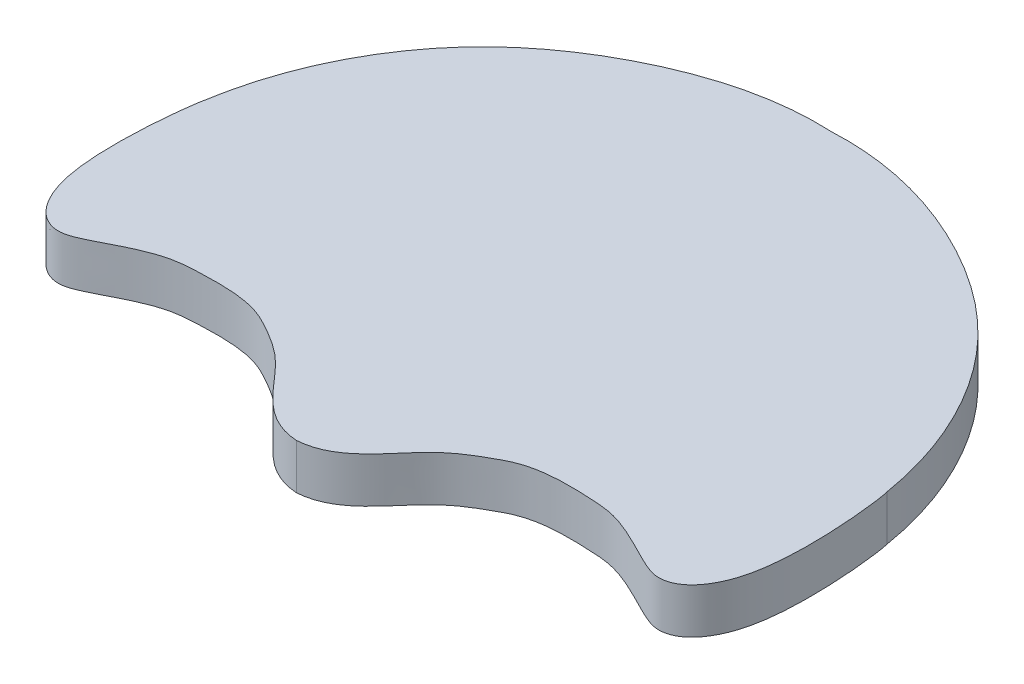
SolidWorks part; units mm, degrees
material "6061-T6 (SS)"
ref_plane "Front Plane" through (0, 0, 0) normal (0, 0, 1) x (1, 0, 0)
ref_plane "Top Plane" through (0, 0, 0) normal (0, 1, 0) x (1, 0, 0)
ref_plane "Right Plane" through (0, 0, 0) normal (1, 0, 0) x (0, 0, -1)
sketch "Sketch3" plane through (0, 0, 0) normal (0, 1, 0) x (1, 0, 0)
  line L0 (0, 0) -> (0, 159.1899) construction
  line L1 (0, 0) -> (0, -140.5301) construction
  line L2 (0, 0) -> (-190.5, 0) construction
  line L3 (0, 0) -> (190.5, 0) construction
  spline S0 degree 3 poles (-190.5, 0) (-184.3927, 37.537) (-157.2613, 93.9641) (-82.3875, 146.6227) (-31.3114, 160.7999) (0, 159.1899) knots 0 0 0 0 0.424401 0.65637 1 1 1 1
  spline S1 degree 3 poles (-190.5, 0) (-192.064, -4.9635) (-201.9672, -83.3146) (-174.6966, -109.29) (-151.6301, -100.568) (-131.4108, -87.7198) (-96.8436, -85.3754) (-78.6925, -86.2588) (-58.8335, -96.8794) (-37.3059, -109.9358) (-21.3496, -139.1148) (0, -140.5301) knots 0 0 0 0 0.166997 0.292321 0.319633 0.426735 0.458914 0.609242 0.64191 0.766802 1 1 1 1
  spline S2 degree 3 poles (190.5, 0) (192.064, -4.9635) (201.9672, -83.3146) (174.6966, -109.29) (151.6301, -100.568) (131.4108, -87.7198) (96.8436, -85.3754) (78.6925, -86.2588) (58.8335, -96.8794) (37.3059, -109.9358) (21.3496, -139.1148) (0, -140.5301) knots 0 0 0 0 0.166997 0.292321 0.319633 0.426735 0.458914 0.609242 0.64191 0.766802 1 1 1 1
  spline S3 degree 3 poles (190.5, 0) (184.3927, 37.537) (157.2613, 93.9641) (82.3875, 146.6227) (31.3114, 160.7999) (0, 159.1899) knots 0 0 0 0 0.424401 0.65637 1 1 1 1
  dimension "D1" = 381
  dimension "D2" = 299.72
  dimension "D3" = 159.1899
  dimension "D4" = 86.8953
  dimension "D5" = 104.4979
  dimension "D6" = 29.1616
  dimension "D7" = 92.2742
  dimension "D8" = 108.411
  dimension "D9" = 67.4883
  dimension "D10" = 43.7314
  dimension "D11" = 117.6915
  dimension "D12" = 162.2568
  dimension "D13" = 89.4522
  dimension "D14" = 140.1036
  dimension "D15" = 175.0666
  dimension "D16" = 50.2669
  dimension "D17" = 101.3666
  dimension "D18" = 138.1225
  dimension "D19" = 155.1557
  dimension "D20" = 192.0074
  dimension "D21" = 193.9268
  dimension "D23" = 76.6666
extrude "Boss-Extrude1" add sketch "Sketch3" along normal blind 25.4 from surface starting at plane "Top Plane"
sketch "Sketch5" plane through (0, 0, 0) normal (0, -1, 0) x (1, 0, 0)
  line L0 (0, 0) -> (0, -20.32) construction
  line L1 (31.75, -52.07) -> (-31.75, -52.07)
  line L2 (31.75, -52.07) -> (31.75, 11.43)
  line L3 (31.75, 11.43) -> (-31.75, 11.43)
  line L4 (-31.75, -52.07) -> (-31.75, 11.43)
  line L5 (31.75, -52.07) -> (-31.75, 11.43) construction
  line L6 (31.75, 11.43) -> (-31.75, -52.07) construction
  line L7 (-31.75, -52.07) -> (-31.75, -30.48)
  line L8 (-31.75, -30.48) -> (31.75, -30.48) construction
  line L9 (0, -20.32) -> (140.7253, -20.32) construction
  line L10 (0, -20.32) -> (0, -97.1287) construction
  line L11 (0, -20.32) -> (31.9753, -118.7297) construction
  line L13 (0, -20.32) -> (63.8443, -108.1942) construction
  line L14 (0, -20.32) -> (95.5392, -89.7333) construction
  line L15 (124.7166, -60.8429) -> (0, -20.32) construction
  line L16 (0, -20.32) -> (154.5508, 21.0918) construction
  line L17 (0, -20.32) -> (148.922, 65.6601) construction
  line L18 (0, -20.32) -> (-31.9753, -118.7297) construction
  line L19 (0, -20.32) -> (-63.8443, -108.1942) construction
  line L20 (0, -20.32) -> (-95.5392, -89.7333) construction
  line L21 (-124.7166, -60.8429) -> (0, -20.32) construction
  line L22 (0, -20.32) -> (-154.5508, 21.0918) construction
  line L23 (0, -20.32) -> (-148.922, 65.6601) construction
  spline S0 degree 3 poles (-148.922, 65.6601) (-157.8584, 40.2253) (-156.2837, 8.5854) (-143.1202, -28.9506) (-139.3242, -37.3463) (-130.3709, -53.1962) (-125.215, -60.649) (-118.0488, -69.1403) (-116.5795, -70.7975) (-113.5719, -74.0252) (-112.0368, -75.592) (-107.2801, -80.2116) (-103.9215, -83.1695) (-93.3361, -91.6595) (-85.5959, -96.8074) (-76.3408, -101.9556) (-75.3049, -102.5187) (-73.219, -103.6268) (-72.1677, -104.1726) (-69.0049, -105.7765) (-66.8862, -106.8006) (-60.5068, -109.7299) (-56.2231, -111.4921) (-47.6308, -114.6027) (-43.3223, -115.9511) (-34.7104, -118.209) (-30.4072, -119.1185) (-21.8242, -120.4791) (-17.5446, -120.9304) (-11.1443, -121.2499) (-9.0138, -121.2968) (-5.8216, -121.2757) (-4.1848, -121.2414) (-2.5489, -121.1705) (-1.9677, -121.1408) (-1.9605, -121.1404) (-1.2995, -121.1064) (-0.6497, -121.073) (0, -121.0396) knots -0.292878 -0.292878 -0.292878 -0.292878 0.125 0.125 0.25 0.25 0.375 0.375 0.40625 0.40625 0.4375 0.4375 0.5 0.5 0.625 0.625 0.640625 0.640625 0.65625 0.65625 0.6875 0.6875 0.75 0.75 0.8125 0.8125 0.875 0.875 0.9375 0.9375 0.96875 0.96875 0.984375 0.992798 0.992798 0.99292 0.99292 1 1 1 1
  spline S5 degree 3 poles (998.6789, -69.6893) (665.1581, -86.8384) (331.6156, -103.9885) (-1.9268, -121.1387) (-1.9605, -121.1404) (-1.9677, -121.1408) (-2.5489, -121.1705) (-4.1848, -121.2414) (-5.8216, -121.2757) (-9.0138, -121.2968) (-11.1443, -121.2499) (-17.5446, -120.9304) (-21.8242, -120.4791) (-30.4072, -119.1185) (-34.7104, -118.209) (-43.3223, -115.9511) (-47.6308, -114.6027) (-56.2231, -111.4921) (-60.5068, -109.7299) (-66.8862, -106.8006) (-69.0049, -105.7765) (-72.1677, -104.1726) (-73.219, -103.6268) (-75.3049, -102.5187) (-76.3408, -101.9556) (-85.5959, -96.8074) (-93.3361, -91.6595) (-103.9215, -83.1695) (-107.2801, -80.2116) (-112.0368, -75.592) (-113.5719, -74.0252) (-116.5795, -70.7975) (-118.0488, -69.1403) (-125.215, -60.649) (-130.3709, -53.1962) (-139.3242, -37.3463) (-143.1202, -28.9506) (-198.5095, 128.9933) (-22.362, 351.6373) (651.8169, -587.5188) knots -3.627409 -3.627409 -3.627409 -3.627409 0.006836 0.00708 0.00708 0.007202 0.007202 0.015625 0.03125 0.03125 0.0625 0.0625 0.125 0.125 0.1875 0.1875 0.25 0.25 0.3125 0.3125 0.34375 0.34375 0.359375 0.359375 0.375 0.375 0.5 0.5 0.5625 0.5625 0.59375 0.59375 0.625 0.625 0.75 0.75 0.875 0.875 3.034324 3.034324 3.034324 3.034324 only from (0, -121.0396) to (-152.8945, 6.1184)
  spline S6 degree 3 poles (-1687.8289, -2297.0686) (-150.4269, 537.0593) (218.9922, 187.4002) (143.1202, -28.9506) (139.3242, -37.3463) (130.3709, -53.1962) (125.215, -60.649) (118.0488, -69.1403) (116.5795, -70.7975) (113.5719, -74.0252) (112.0368, -75.592) (107.2801, -80.2116) (103.9215, -83.1695) (93.3361, -91.6595) (85.5959, -96.8074) (76.3408, -101.9556) (75.3049, -102.5187) (73.219, -103.6268) (72.1677, -104.1726) (69.0049, -105.7765) (66.8862, -106.8006) (60.5068, -109.7299) (56.2231, -111.4921) (47.6308, -114.6027) (43.3223, -115.9511) (34.7104, -118.209) (30.4072, -119.1185) (21.8242, -120.4791) (17.5446, -120.9304) (11.1443, -121.2499) (9.0138, -121.2968) (5.8216, -121.2757) (4.1848, -121.2414) (2.5489, -121.1705) (1.9677, -121.1408) (1.9605, -121.1404) (-997.3522, -69.7575) (-1996.6535, -18.3753) (-2996.029, 33.0152) knots -2.879056 -2.879056 -2.879056 -2.879056 0.125 0.125 0.25 0.25 0.375 0.375 0.40625 0.40625 0.4375 0.4375 0.5 0.5 0.625 0.625 0.640625 0.640625 0.65625 0.65625 0.6875 0.6875 0.75 0.75 0.8125 0.8125 0.875 0.875 0.9375 0.9375 0.96875 0.96875 0.984375 0.992798 0.992798 0.99292 0.99292 11.881939 11.881939 11.881939 11.881939 only from (152.8945, 6.1184) to (0, -121.0396)
  spline S8 degree 3 poles (148.922, 65.6601) (157.8584, 40.2253) (156.2837, 8.5854) (143.1202, -28.9506) (139.3242, -37.3463) (130.3709, -53.1962) (125.215, -60.649) (118.0488, -69.1403) (116.5795, -70.7975) (113.5719, -74.0252) (112.0368, -75.592) (107.2801, -80.2116) (103.9215, -83.1695) (93.3361, -91.6595) (85.5959, -96.8074) (76.3408, -101.9556) (75.3049, -102.5187) (73.219, -103.6268) (72.1677, -104.1726) (69.0049, -105.7765) (66.8862, -106.8006) (60.5068, -109.7299) (56.2231, -111.4921) (47.6308, -114.6027) (43.3223, -115.9511) (34.7104, -118.209) (30.4072, -119.1185) (21.8242, -120.4791) (17.5446, -120.9304) (11.1443, -121.2499) (9.0138, -121.2968) (5.8216, -121.2757) (4.1848, -121.2414) (2.5489, -121.1705) (1.9677, -121.1408) (1.9605, -121.1404) (1.2995, -121.1064) (0.6497, -121.073) (0, -121.0396) knots -0.292878 -0.292878 -0.292878 -0.292878 0.125 0.125 0.25 0.25 0.375 0.375 0.40625 0.40625 0.4375 0.4375 0.5 0.5 0.625 0.625 0.640625 0.640625 0.65625 0.65625 0.6875 0.6875 0.75 0.75 0.8125 0.8125 0.875 0.875 0.9375 0.9375 0.96875 0.96875 0.984375 0.992798 0.992798 0.99292 0.99292 1 1 1 1
  point P0 (0, -20.32)
  point P3 (0, -20.32)
  point P14 (0, 114.3)
  point P16 (0, 88.9)
  dimension "D1" = 20.32
  dimension "D2" = 63.5
  dimension "D3" = 63.5
  dimension "D4" = 21.59
  dimension "D6" = 25.4
  dimension "D7" = 88.9
  dimension "D8" = 18
  dimension "D9" = 18
  dimension "D10" = 18
  dimension "D11" = 18
  dimension "D12" = 15
  dimension "D13" = 15
  dimension "D5" = 38.1
equation "\"Plate thickness\"=1"
equation "\"D1@Boss-Extrude1\"=\"Plate thickness\""
equation "\"Bracket Alignment\"= .80"
equation "\"D1@Sketch5\"=\"Bracket Alignment\""
